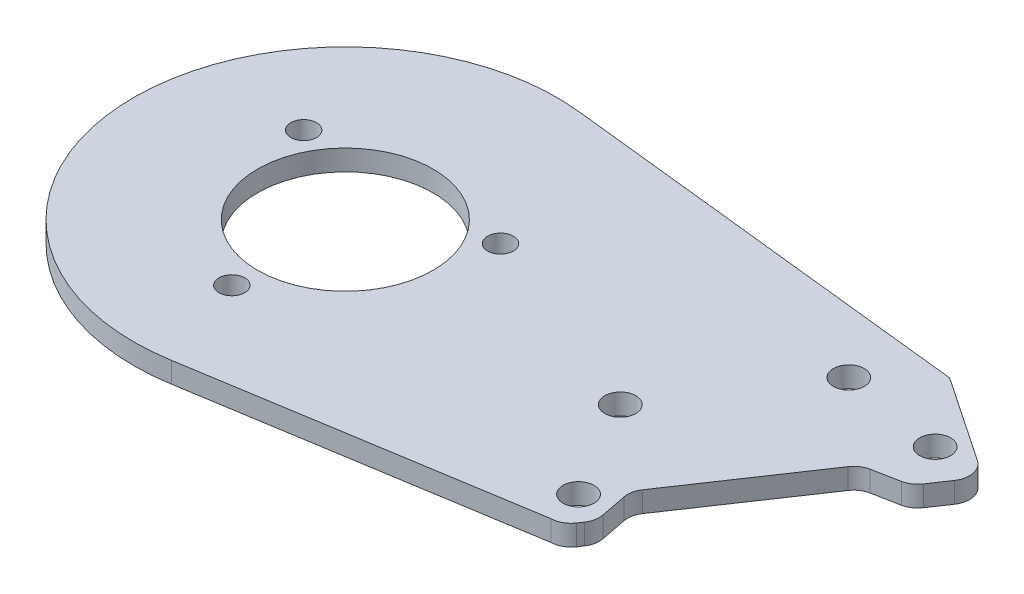
SolidWorks part; units mm, degrees
ref_plane "前视基准面" through (0, 0, 0) normal (0, 0, 1) x (1, 0, 0)
ref_plane "上视基准面" through (0, 0, 0) normal (0, 1, 0) x (1, 0, 0)
ref_plane "右视基准面" through (0, 0, 0) normal (1, 0, 0) x (0, 0, -1)
sketch "Sketch1" plane through (0, 0, 0) normal (0, 1, 0) x (1, 0, 0)
  line L4 (-74.3789, -34.0492) -> (-72.703, -31.561) construction
  line L5 (-93.6269, -57.2553) -> (-125.2852, -62.3534)
  line L6 (-86.1081, -26.1406) -> (-76.1604, -32.8494)
  line L7 (-86.1081, -26.1406) -> (-126.3738, -21.7577)
  line L16 (-83.1176, -37.8089) -> (-78.9535, -36.9965)
  line L17 (-76.1604, -32.8494) -> (-78.9535, -36.9965)
  line L18 (-83.1176, -37.8089) -> (-92.0556, -51.0797)
  line L19 (-91.2432, -55.2438) -> (-92.0556, -51.0797)
  line L22 (-91.2432, -55.2438) -> (-92.919, -57.7321)
  line L24 (-92.919, -57.7321) -> (-93.6269, -57.2553)
  arc A5 (-148.0299, -48.8087) -> (-125.2852, -62.3534) centre (-128.648, -42.1311) ccw
  arc A6 (-126.3738, -21.7577) -> (-148.0299, -48.8087) centre (-128.648, -42.1311) ccw
  arc A10 (-128.0147, -54.2132) -> (-129.2661, -52.049) centre (-128.6404, -53.1311) ccw
  arc A11 (-129.2661, -52.049) -> (-128.0147, -54.2132) centre (-128.6404, -53.1311) ccw
  arc A12 (-118.4997, -37.7067) -> (-119.7512, -35.5425) centre (-119.1255, -36.6246) ccw
  arc A13 (-119.7512, -35.5425) -> (-118.4997, -37.7067) centre (-119.1255, -36.6246) ccw
  arc A14 (-137.5523, -37.7198) -> (-138.8038, -35.5556) centre (-138.178, -36.6377) ccw
  arc A15 (-138.8038, -35.5556) -> (-137.5523, -37.7198) centre (-138.178, -36.6377) ccw
  arc A23 (-132.903, -34.7728) -> (-124.3929, -49.4894) centre (-128.648, -42.1311) ccw
  arc A24 (-124.3929, -49.4894) -> (-132.903, -34.7728) centre (-128.648, -42.1311) ccw
  point P4 (-78.4629, -50.5891)
extrude "Boss-Extrude1" add sketch "Sketch1" along normal blind 2
sketch "Sketch2" plane through (0, 2, 0) normal (0, 1, 0) x (1, 0, 0)
  circle A0 centre (-94.3193, -53.8718) radius 1.5
  circle A1 centre (-81.0356, -32.6156) radius 1.5
  circle A2 centre (-99.8164, -44.3284) radius 1.5
  circle A3 centre (-91.0265, -30.9865) radius 1.5
extrude "Cut-Extrude1" cut sketch "Sketch2" against normal through all
fillet "Fillet1" radius 2 6 edges at (-76.1604, 1, 32.8494) (-78.9535, 1, 36.9965) (-83.1176, 1, 37.8089) (-92.919, 1, 57.7321) (-91.2432, 1, 55.2438) (-92.0556, 1, 51.0797)
